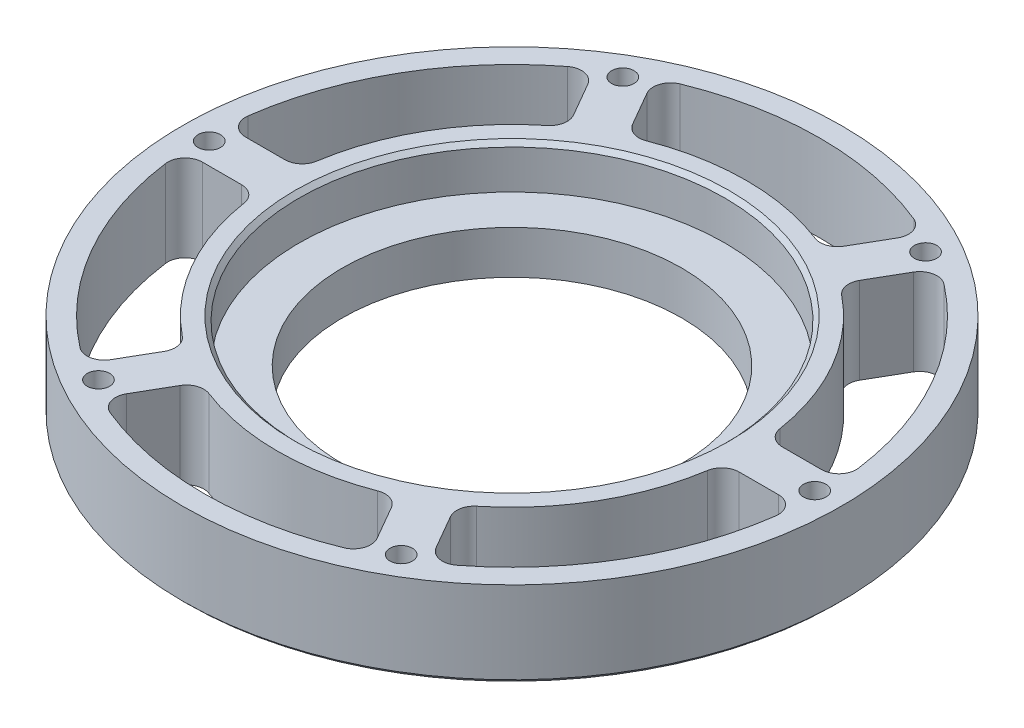
SolidWorks part; units mm, degrees
ref_plane "Front Plane" through (0, 0, 0) normal (0, 0, 1) x (1, 0, 0)
ref_plane "Top Plane" through (0, 0, 0) normal (0, 1, 0) x (1, 0, 0)
ref_plane "Right Plane" through (0, 0, 0) normal (1, 0, 0) x (0, 0, -1)
sketch "Sketch2" plane through (0, 0, 0) normal (1, 0, 0) x (0, 0, -1)
  line L0 (-39.2125, 0) -> (-76.2, 0)
  line L1 (-76.2, 0) -> (-76.2, 20)
  line L2 (-76.2, 20) -> (-49.2125, 20)
  line L3 (-49.2125, 20) -> (-49.2125, 10)
  line L4 (-49.2125, 10) -> (-39.2125, 10)
  line L5 (-39.2125, 10) -> (-39.2125, 0)
  dimension "D1" = 76.2
  dimension "D2" = 20
  dimension "D3" = 10
  dimension "D4" = 49.2125
  dimension "D5" = 10
ref_axis "Axis1" through (0, -1, 0) along (0, 1, 0)
revolve "Revolve1" add sketch "Sketch2" angle 360 about axis through (0, -1, 0) along (0, 1, 0)
hole_wizard "#6 (0.204) Diameter Hole1" positions "Sketch6" profile "Sketch7" hole size "#6" standard "ANSI Inch" end condition through all
sketch "Sketch6" plane through (0, 20, 0) normal (0, 1, 0) x (1, 0, 0)
  line L0 (0, 0) -> (-69.8201, 120.932) construction
  line L2 (0, 0) -> (0, 109.0908) construction
  point P0 (-35, 60.6218)
  dimension "D1" = 30
  dimension "D2" = 70
sketch "Sketch7" plane through (-35, 20, -60.6218) normal (1, 0, 0) x (0, 0, 1)
  line L0 (0, 0) -> (0, 20)
  line L1 (0, 20) -> (2.5908, 20)
  line L2 (2.5908, 20) -> (2.5908, 0)
  line L5 (2.5908, 0) -> (0, 0)
  line L11 (0, -6.35) -> (0, 107.95) construction
  dimension "Thru Hole Dia." = 5.1816
  dimension "Thru Hole Depth" = 20
pattern_circular "CirPattern3" count 6 over 360 about axis through (0, -1, 0) along (0, 1, 0) of "#6 (0.204) Diameter Hole1"
sketch "Sketch8" plane through (0, 20, 0) normal (0, 1, 0) x (1, 0, 0)
  line L0 (-31.182, 64.0088) -> (-22.6606, 49.2493)
  line L1 (31.182, 64.0088) -> (22.6606, 49.2493)
  line L2 (0, 0) -> (-35, 60.6218) construction
  line L4 (0, 0) -> (0, 93.9995) construction
  arc A0 (-22.6606, 49.2493) -> (22.6606, 49.2493) centre (0, 0) cw
  arc A1 (-31.182, 64.0088) -> (31.182, 64.0088) centre (0, 0) cw
  circle A2 centre (0, 0) radius 49.2125 construction
  circle A3 centre (0, 0) radius 76.2 construction
  dimension "D1" = 5
  dimension "D2" = 5
  dimension "D3" = 5
extrude "Cut-Extrude1" cut sketch "Sketch8" against normal through all
fillet "Fillet1" radius 4 4 edges at (31.182, 10, -64.0088) (22.6606, 10, -49.2493) (-31.182, 10, -64.0088) (-22.6606, 10, -49.2493)
pattern_circular "CirPattern4" count 6 over 360 about axis through (0, -1, 0) along (0, 1, 0) of "Cut-Extrude1", "Fillet1"
chamfer "Chamfer1" distance 1 angle 45 1 edges at (0, 20, -49.2125)
chamfer "Chamfer2" distance 1 angle 45 1 edges at (0, 0, -76.2)
equation "\"TubeDiameter\" = 6.000in"
equation "\"D1@Sketch2\"=\"TubeDiameter\"/2"
